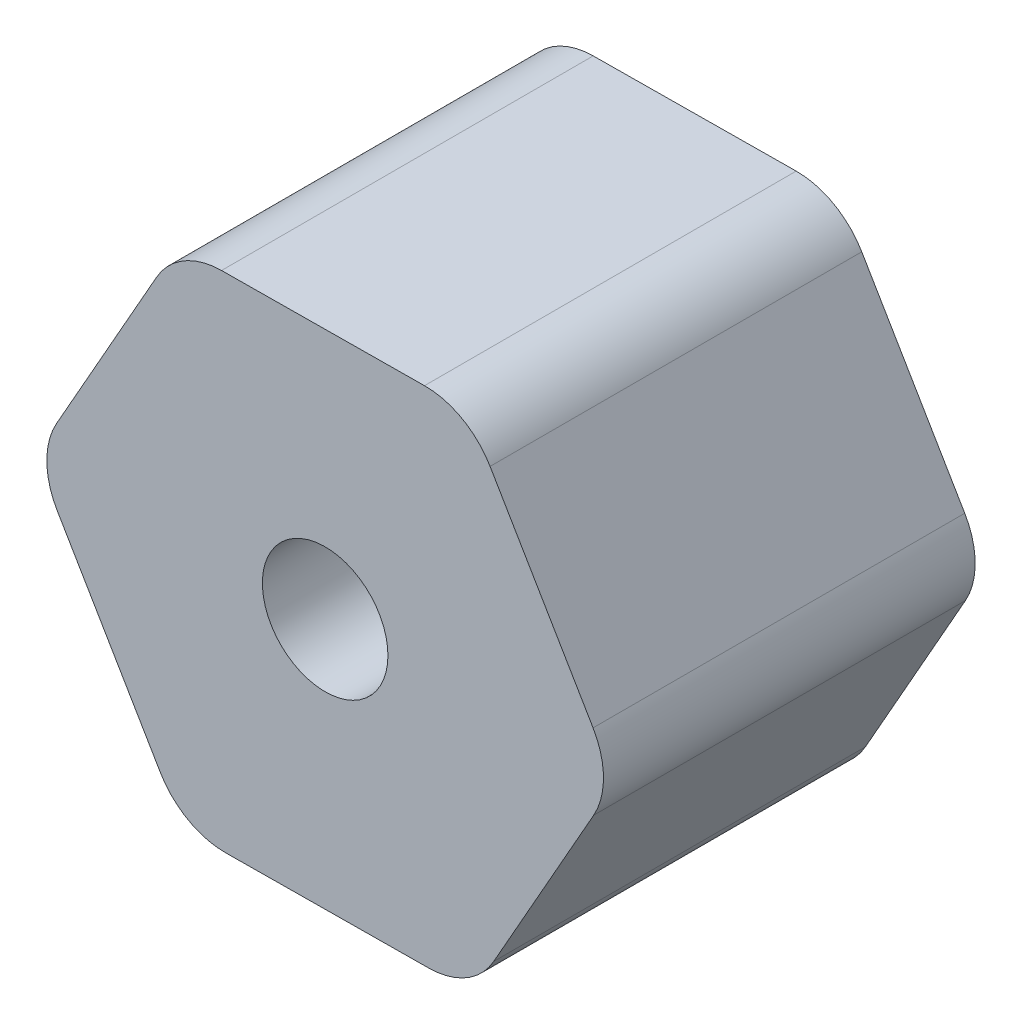
SolidWorks part; units mm, degrees
ref_plane "Alzado" through (0, 0, 0) normal (0, 0, 1) x (1, 0, 0)
ref_plane "Planta" through (0, 0, 0) normal (0, 1, 0) x (1, 0, 0)
ref_plane "Vista lateral" through (0, 0, 0) normal (1, 0, 0) x (0, 0, -1)
sketch "Croquis1" plane through (0, 0, 0) normal (0, 0, 1) x (1, 0, 0)
  line L1 (3.9563, 10.034) -> (-4.1263, 9.9653)
  line L2 (-6.7115, 8.4433) -> (-10.6933, 1.4092)
  line L3 (-10.6679, -1.5907) -> (-6.5671, -8.5561)
  line L4 (-3.9563, -10.034) -> (4.1263, -9.9653)
  line L5 (6.7115, -8.4433) -> (10.6933, -1.4092)
  line L6 (10.6679, 1.5907) -> (6.5671, 8.5561)
  circle A0 centre (0, 0) radius 2.5
  circle A1 centre (0, 0) radius 10 construction
  arc A2 (-4.1263, 9.9653) -> (-6.7115, 8.4433) centre (-4.1008, 6.9654) ccw
  arc A3 (3.9563, 10.034) -> (6.5671, 8.5561) centre (3.9818, 7.0341) cw
  arc A4 (10.6933, -1.4092) -> (10.6679, 1.5907) centre (8.0826, 0.0687) ccw
  arc A5 (4.1263, -9.9653) -> (6.7115, -8.4433) centre (4.1008, -6.9654) ccw
  arc A6 (-6.5671, -8.5561) -> (-3.9563, -10.034) centre (-3.9818, -7.0341) ccw
  arc A7 (-10.6933, 1.4092) -> (-10.6679, -1.5907) centre (-8.0826, -0.0687) ccw
  dimension "D1" = 20
  dimension "D2" = 5
  dimension "D3" = 3
extrude "Saliente-Extruir1" add sketch "Croquis1" along normal blind 14.8
